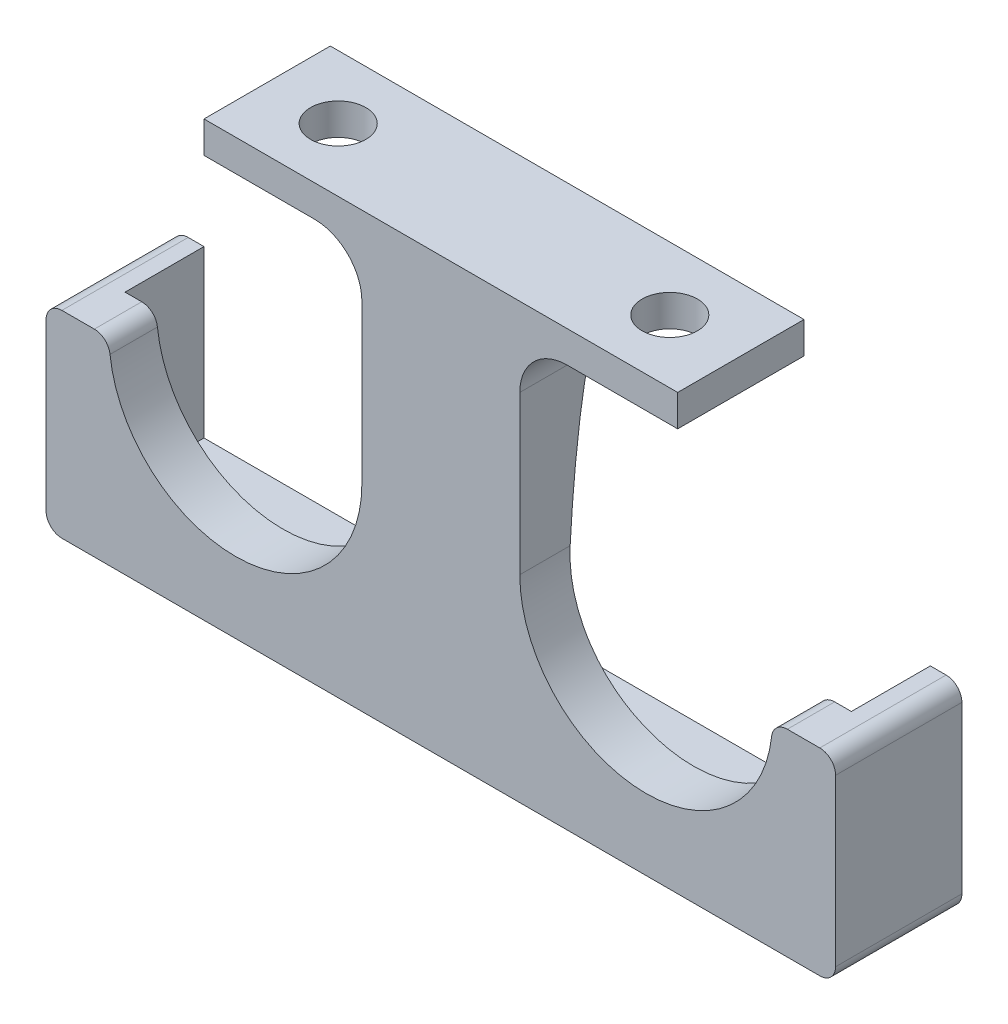
SolidWorks part; units mm, degrees
ref_plane "Plan de face" through (0, 0, 0) normal (0, 0, 1) x (1, 0, 0)
ref_plane "Plan de dessus" through (0, 0, 0) normal (0, 1, 0) x (1, 0, 0)
ref_plane "Plan de droite" through (0, 0, 0) normal (1, 0, 0) x (0, 0, -1)
sketch "Esquisse1" plane through (0, 0, 0) normal (0, 0, 1) x (1, 0, 0)
  line L0 (-21, 0) -> (-25, 0)
  line L1 (-25, 0) -> (-25, -12.5)
  line L2 (-25, -12.5) -> (25, -12.5)
  line L3 (25, -12.5) -> (25, 0)
  line L4 (25, 0) -> (21, 0)
  line L6 (-5, 0) -> (-5, 13)
  line L7 (-5, 13) -> (5, 13)
  line L8 (5, 13) -> (5, 0)
  arc A0 (-21, 0) -> (-5, 0) centre (-13, 0) ccw
  arc A1 (5, 0) -> (21, 0) centre (13, 0) ccw
  dimension "D2" = 16
  dimension "D1" = 26
  dimension "D3" = 12
  dimension "D4" = 12
  dimension "D5" = 13
  dimension "D6" = 12.5
  dimension "D7" = 13
extrude "Boss.-Extru.1" add sketch "Esquisse1" along normal blind 3
sketch "Esquisse3" plane through (0, 0, 0) normal (0, 0, -1) x (-1, 0, 0)
  line L11 (-25, -12.5) -> (-25, 0) construction
  line L12 (25, -12.5) -> (-25, -12.5) construction
  line L13 (25, 0) -> (25, -12.5) construction
  line L14 (-23, -10.5) -> (-23, 0)
  line L15 (23, 0) -> (23, -10.5)
  line L16 (23, -10.5) -> (-23, -10.5)
  line L17 (-23, -10.5) -> (-23, 0)
  line L18 (23, 0) -> (23, -10.5)
  line L19 (23, -10.5) -> (-23, -10.5)
  line L20 (-25, -12.5) -> (-25, 0)
  line L21 (25, -12.5) -> (-25, -12.5)
  line L22 (25, 0) -> (25, -12.5)
  line L23 (25, 0) -> (23, 0)
  line L24 (-23, 0) -> (-25, 0)
  dimension "D1" = 2
extrude "Boss.-Extru.2" add sketch "Esquisse3" along normal blind 5
sketch "Esquisse4" plane through (0, 13, 0) normal (0, 1, 0) x (1, 0, 0)
  line L5 (-23, 5) -> (23, 5) construction
  line L6 (-15, -3) -> (15, -3)
  line L10 (-15, -3) -> (-15, 5)
  line L11 (-15, 5) -> (15, 5)
  line L12 (15, -3) -> (15, 5)
  line L13 (-15, -3) -> (15, 5) construction
  line L14 (-15, 5) -> (15, -3) construction
  circle A2 centre (-10.5, 1) radius 1.75
  circle A3 centre (10.5, 1) radius 1.75
  point P0 (0, 1)
  dimension "D2" = 30
  dimension "D3" = 3.5
  dimension "D1" = 8
  dimension "D4" = 4.5
  dimension "D5" = 4.5
extrude "Boss.-Extru.3" add sketch "Esquisse4" along normal blind 2 contours L12 L11 L10 L6 | A2 | A3
fillet "Congé1" radius 20 1 edges at (0, 13, 0) second distance 3 first distance on face at (0, -1.1, 0)
fillet "Congé2" radius 3 2 edges
fillet "Congé3" radius 1 6 edges at (21, 0, 1.5) (-21, 0, 1.5) (-25, 0, -1) (-25, -12.5, -1) (25, 0, -1) (25, -12.5, -1)
